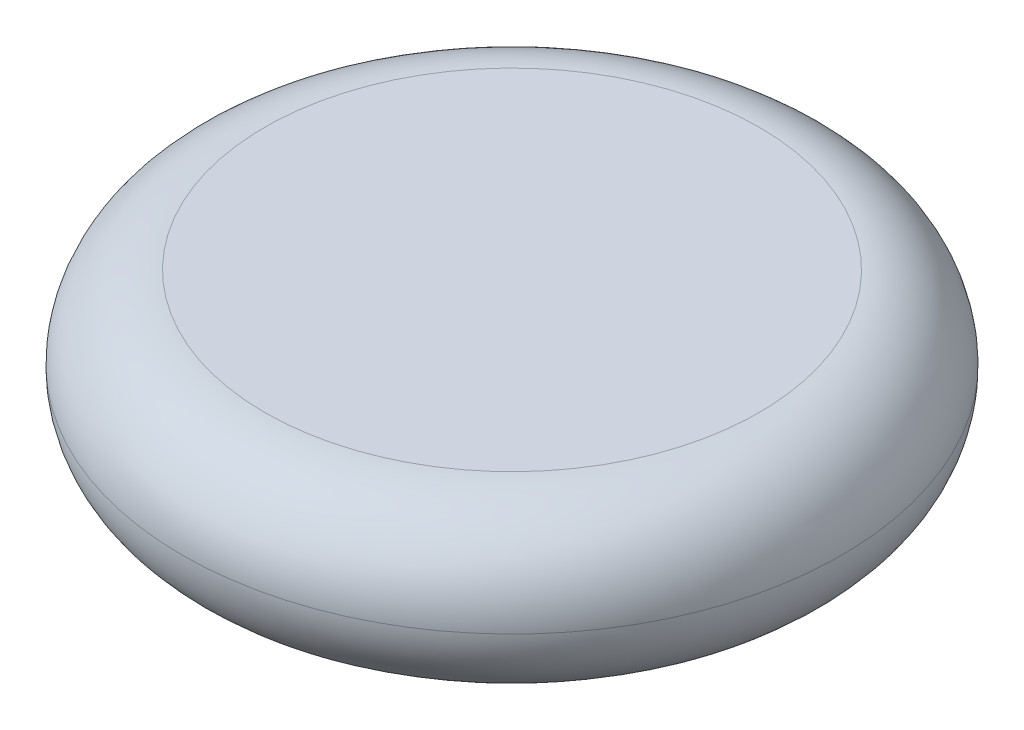
SolidWorks part; units mm, degrees
ref_plane "Front Plane" through (0, 0, 0) normal (0, 0, 1) x (1, 0, 0)
ref_plane "Top Plane" through (0, 0, 0) normal (0, 1, 0) x (1, 0, 0)
ref_plane "Right Plane" through (0, 0, 0) normal (1, 0, 0) x (0, 0, -1)
sketch "Sketch1" plane through (0, 0, 0) normal (0, 1, 0) x (1, 0, 0)
  circle A0 centre (0, 0) radius 203.2
  dimension "D1" = 406.4
extrude "Boss-Extrude1" add sketch "Sketch1" along normal blind 50.8 and the other way blind 50.8 contours A0
fillet "Fillet1" radius 50.8 2 edges at (0, -50.8, 203.2) (0, 50.8, 203.2)
equation "\"wheel_dia\" = 16in"
equation "\"wheel_width\"= 4in"
equation "\"D1@Sketch1\"=\"wheel_dia\""
equation "\"D1@Boss-Extrude1\"=\"wheel_width\"/2"
equation "\"D1@Fillet1\"=\"wheel_width\"/2"
equation "\"D2@Boss-Extrude1\"=\"wheel_width\"/2"
